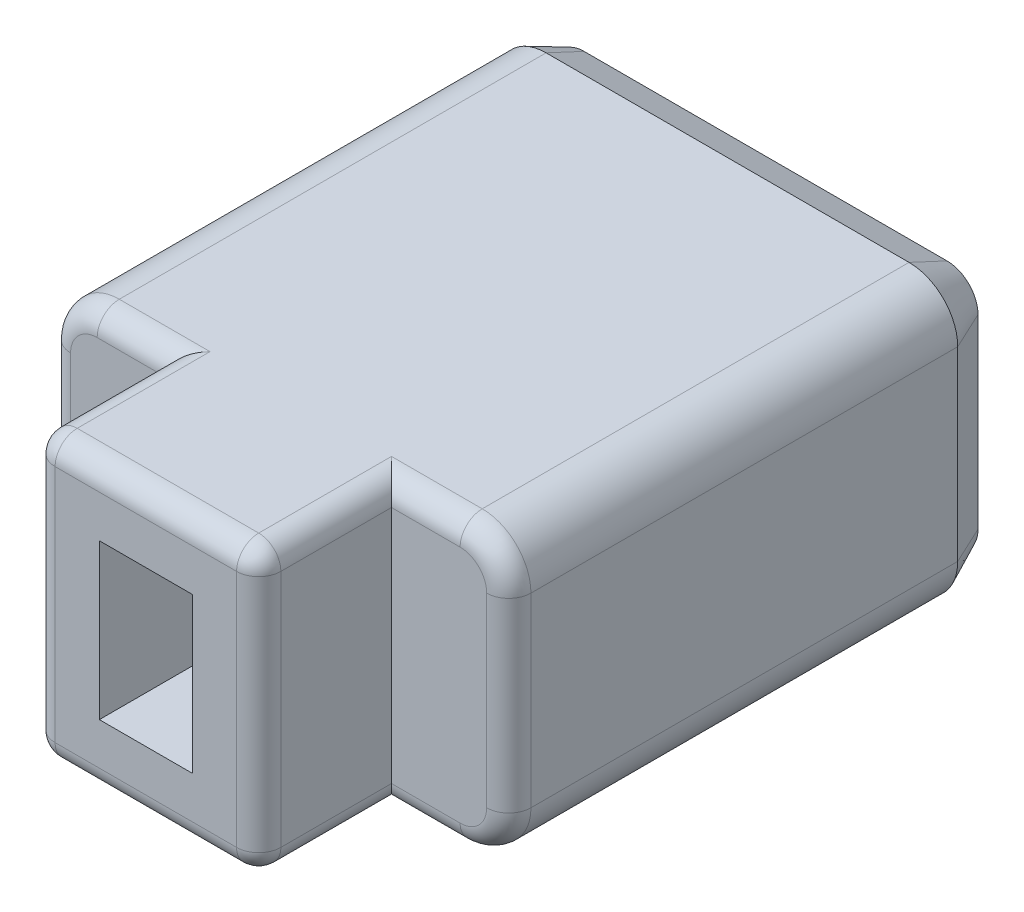
SolidWorks part; units mm, degrees
ref_plane "Plan de face" through (0, 0, 0) normal (0, 0, 1) x (1, 0, 0)
ref_plane "Plan de dessus" through (0, 0, 0) normal (0, 1, 0) x (1, 0, 0)
ref_plane "Plan de droite" through (0, 0, 0) normal (1, 0, 0) x (0, 0, -1)
sketch "Esquisse2" plane through (0, 0, 0) normal (0, 0, 1) x (1, 0, 0)
  line L1 (1.1, 0) -> (9.3, 0)
  line L2 (0, 1.1) -> (0, 5.3)
  line L3 (1.1, 6.4) -> (9.3, 6.4)
  line L4 (10.4, 1.1) -> (10.4, 5.3)
  arc A0 (9.3, 6.4) -> (10.4, 5.3) centre (9.3, 5.3) cw
  arc A1 (9.3, 0) -> (10.4, 1.1) centre (9.3, 1.1) ccw
  arc A2 (1.1, 0) -> (0, 1.1) centre (1.1, 1.1) cw
  arc A3 (0, 5.3) -> (1.1, 6.4) centre (1.1, 5.3) cw
  point P7 (10.4, 6.4)
  point P12 (0, 0)
  point P15 (0, 6.4)
  dimension "D3" = 1.1
  dimension "D1" = 10.4
  dimension "D2" = 6.4
extrude "Boss.-Extru.1" add sketch "Esquisse2" along normal blind 14
sketch "Esquisse3" plane through (0, 0, 14) normal (0, 0, 1) x (1, 0, 0)
  line L0 (0, 5.3) -> (0, 1.1) construction
  line L1 (4.15, 4.95) -> (6.25, 4.95)
  line L2 (4.15, 4.95) -> (4.15, 1.45)
  line L3 (4.15, 1.45) -> (6.25, 1.45)
  line L4 (6.25, 4.95) -> (6.25, 1.45)
  line L5 (10.4, 1.1) -> (10.4, 5.3) construction
  line L6 (9.3, 6.4) -> (1.1, 6.4) construction
  line L7 (1.1, 0) -> (9.3, 0) construction
  dimension "D1" = 2.1
  dimension "D2" = 3.5
  dimension "D3" = 4.15
  dimension "D4" = 4.15
  dimension "D5" = 1.45
  dimension "D6" = 1.45
extrude "Enlèv. mat.-Extru.1" cut sketch "Esquisse3" against normal blind 3
sketch "Esquisse4" plane through (0, 0, 14) normal (0, 0, 1) x (1, 0, 0)
  line L0 (2.65, 6.4) -> (2.65, 0)
  line L1 (9.3, 6.4) -> (1.1, 6.4) construction
  line L2 (1.1, 0) -> (9.3, 0) construction
  line L3 (2.65, 0) -> (7.75, 0)
  line L4 (7.75, 0) -> (7.75, 6.4)
  line L5 (7.75, 6.4) -> (2.65, 6.4)
  line L6 (4.15, 4.95) -> (4.15, 1.45) construction
  line L7 (6.25, 1.45) -> (6.25, 4.95) construction
  dimension "D1" = 1.5
  dimension "D2" = 1.5
extrude "Enlèv. mat.-Extru.2" cut sketch "Esquisse4" against normal blind 3 flip side to cut
fillet "Congé1" radius 0.5 18 edges at (8.525, 0, 11) (10.0778, 0.3222, 11) (10.4, 3.2, 11) (10.0778, 6.0778, 11) (1.875, 6.4, 11) (0.3222, 6.0778, 11) (1.875, 0, 11) (0.3222, 0.3222, 11) (7.75, 6.4, 12.5) (2.65, 6.4, 12.5) (7.75, 0, 12.5) (2.65, 0, 12.5) (2.65, 3.2, 14) (5.2, 6.4, 14) (7.75, 3.2, 14) (5.2, 0, 14) (8.525, 6.4, 11) (0, 3.2, 11)
chamfer "Chanfrein1" distance 0.4 angle 65 8 edges at (5.2, 0, 0) (10.0778, 0.3222, 0) (0.3222, 0.3222, 0) (10.4, 3.2, 0) (0, 3.2, 0) (10.0778, 6.0778, 0) (0.3222, 6.0778, 0) (5.2, 6.4, 0) first distance on face at (5.2, 3.2, 0)
sketch "Esquisse5" plane through (0, 0, 0) normal (0, 0, -1) x (-1, 0, 0)
  line L0 (-0.4, 5.3) -> (-10, 5.3) construction
  arc A0 (-9.3, 6) -> (-10, 5.3) centre (-9.3, 5.3) ccw construction
  text T0 "7" font "Century Gothic" height 4
extrude "Enlèv. mat.-Extru.3" cut sketch "Esquisse5" against normal blind 0.3
extrude "Boss.-Extru.2" add sketch "Esquisse5<2>" along normal blind 0.3 separate body
sketch "Esquisse5<2>" plane through (0, 0, 0) normal (0, 0, -1) x (-1, 0, 0) same geometry as "Esquisse5"
